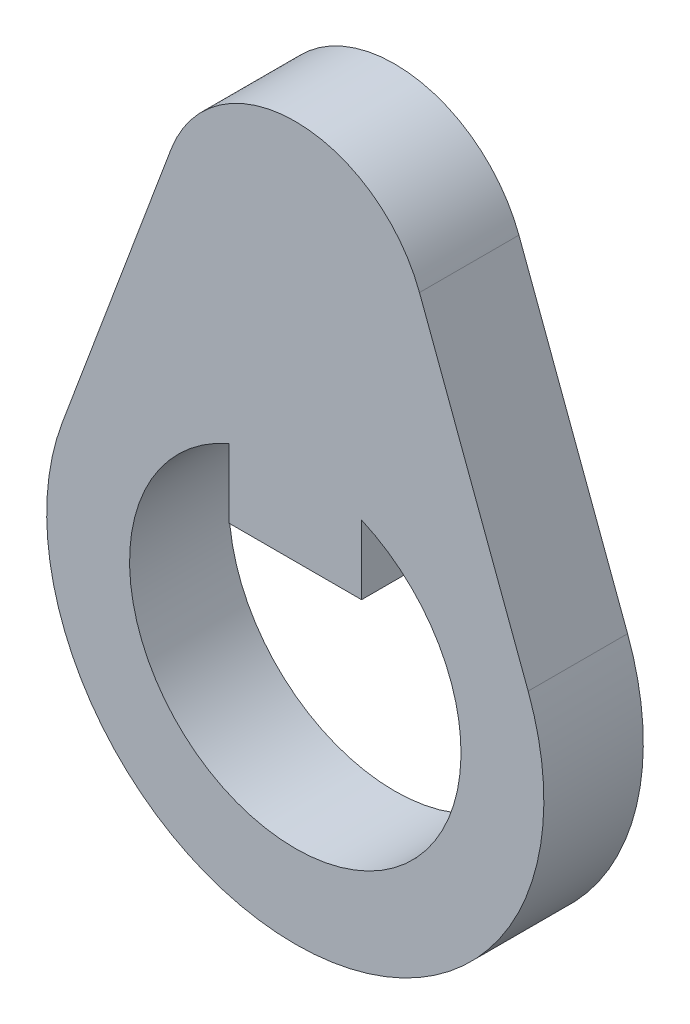
SolidWorks part; units mm, degrees
ref_plane "Front Plane" through (0, 0, 0) normal (0, 0, 1) x (1, 0, 0)
ref_plane "Top Plane" through (0, 0, 0) normal (0, 1, 0) x (1, 0, 0)
ref_plane "Right Plane" through (0, 0, 0) normal (1, 0, 0) x (0, 0, -1)
sketch "Sketch1" plane through (0, 0, 0) normal (0, 0, 1) x (1, 0, 0)
  line L0 (4, 15) -> (-4, 15)
  line L1 (4, 15) -> (4, 5)
  line L2 (4, 5) -> (-4, 5)
  line L3 (-4, 15) -> (-4, 5)
  line L4 (4, 15) -> (-4, 5) construction
  line L5 (4, 5) -> (-4, 15) construction
  line L6 (-7.494, 22.8) -> (-14.0512, 5.25)
  line L7 (7.494, 22.8) -> (14.0512, 5.25)
  circle A1 centre (0, 0) radius 10
  arc A2 (-7.494, 22.8) -> (7.494, 22.8) centre (0, 20) cw
  arc A3 (-14.0512, 5.25) -> (14.0512, 5.25) centre (0, 0) ccw
  point P3 (0, 10)
  dimension "D4" = 20
  dimension "D5" = 15
  dimension "D6" = 8
  dimension "D1" = 20
  dimension "D2" = 8
  dimension "D3" = 10
extrude "Boss-Extrude1" add sketch "Sketch1" along normal blind 6 contours L6 A3 L7 A2 A1 L3 L0 L1 | A1 L1 L0 L3 | L1 A1 L3 L2 region at (0, 12.3575, 0) region at (0, 7.3697, 0) region at (0, 27.4757, 0)
equation "\"shaftDiam\" = 20mm"
equation "\"keyW\" = 8mm"
equation "\"keyL\" = 10mm"
equation "\"clearance\" = .8mm"
equation "\"handleShaftLen\" = 60mm"
equation "\"panelH\" = 80mm"
equation "\"panelW\" = 110mm"
equation "\"D2@Sketch1\"=\"keyW\""
equation "\"D3@Sketch1\"=\"keyL\""
equation "\"D4@Sketch1\"=\"shaftDiam\""
equation "\"D5@Sketch1\"=\"shaftDiam\"*.75"
equation "\"D1@Sketch1\"=\"shaftDiam\""
equation "\"D6@Sketch1\"=\"shaftDiam\"/2.5"
equation "\"D1@Boss-Extrude1\"=\"handleShaftLen\"/10"
